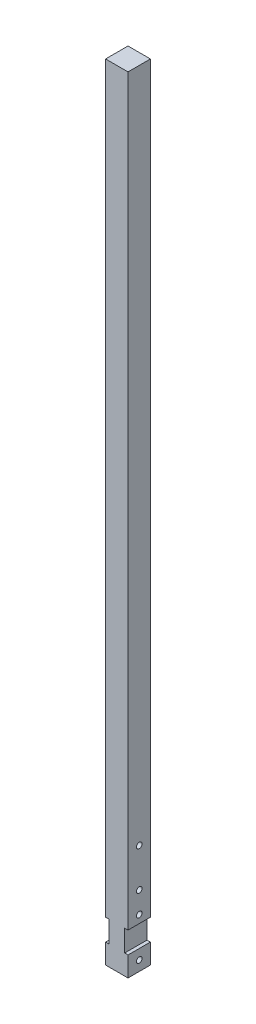
SolidWorks part; units mm, degrees
material "Alliage 1060"
ref_plane "Plan de face" through (0, 0, 0) normal (0, 0, 1) x (1, 0, 0)
ref_plane "Plan de dessus" through (0, 0, 0) normal (0, 1, 0) x (1, 0, 0)
ref_plane "Plan de droite" through (0, 0, 0) normal (1, 0, 0) x (0, 0, -1)
sketch "Esquisse1" plane through (0, 0, 0) normal (0, 1, 0) x (1, 0, 0)
  line L0 (-5, 5) -> (5, -5) construction
  line L1 (-5, 5) -> (5, 5)
  line L2 (-5, 5) -> (-5, -5)
  line L3 (-5, -5) -> (5, -5)
  line L4 (5, 5) -> (5, -5)
  dimension "D1" = 10
extrude "Boss.-Extru.1" add sketch "Esquisse1" along normal blind 350
hole_wizard "Trou taraudé M3x0.51" positions "Esquisse2" profile "Esquisse3" tap size "M3x0.5" standard "Ansi Metric" end condition through all
sketch "Esquisse2" plane through (-5, 0, 0) normal (-1, 0, 0) x (0, 0, 1)
  line L0 (0, 50.3) -> (0, 47.1) construction
  line L1 (-2.6, 50.3) -> (2.9, 50.3) construction
  line L2 (2.9, 47.1) -> (-2.6, 47.1) construction
  line L4 (-2.6, 33.1) -> (2.9, 33.1) construction
  line L6 (0, 33.1) -> (0, 29.9) construction
  line L7 (2.9, 29.9) -> (-2.6, 29.9) construction
  point P0 (0, 22)
  point P3 (0, 4.45)
  point P6 (0, 31.5)
  point P8 (0, 48.7)
  point P27 (0.8398, 48.7)
  point P28 (0.8398, 31.5)
sketch "Esquisse3" plane through (-5, 22, 0) normal (0, 1, 0) x (0, 0, 1)
  line L0 (0, 0) -> (0, 10)
  line L1 (0, 10) -> (1.25, 10)
  line L2 (1.25, 10) -> (1.25, 0)
  line L5 (1.25, 0) -> (0, 0)
  line L11 (0, -6.35) -> (0, 107.95) construction
  dimension "Diamètre du trou pour taraudage jusqu'au prochain" = 2.5
  dimension "Profondeur du trou pour taraudage jusqu'au prochain" = 10
cosmetic thread "Filetage de perçage1"
cosmetic thread "Filetage de perçage2"
cosmetic thread "Filetage de perçage3"
cosmetic thread "Filetage de perçage4"
sketch "Esquisse4" plane through (0, 0, -5) normal (0, 0, -1) x (-1, 0, 0)
  line L0 (5, 350) -> (5, 0) construction
  line L1 (5, 18.5) -> (3.5, 18.5)
  line L2 (5, 18.5) -> (5, 8.9)
  line L3 (5, 8.9) -> (3.5, 8.9)
  line L4 (3.5, 18.5) -> (3.5, 8.9)
  line L5 (-3.5, 18.5) -> (-5, 18.5)
  line L6 (-3.5, 18.5) -> (-3.5, 8.9)
  line L7 (-3.5, 8.9) -> (-5, 8.9)
  line L8 (-5, 18.5) -> (-5, 8.9)
  line L9 (5, 18.5) -> (7.6438, 18.5) construction
  line L10 (5, 8.9) -> (8.1439, 8.9) construction
  line L11 (-5, 350) -> (-5, 0) construction
  point P16 (3.3608, 18.5)
  dimension "D1" = 1.5
extrude "Enlèv. mat.-Extru.1" cut sketch "Esquisse4" against normal through all
